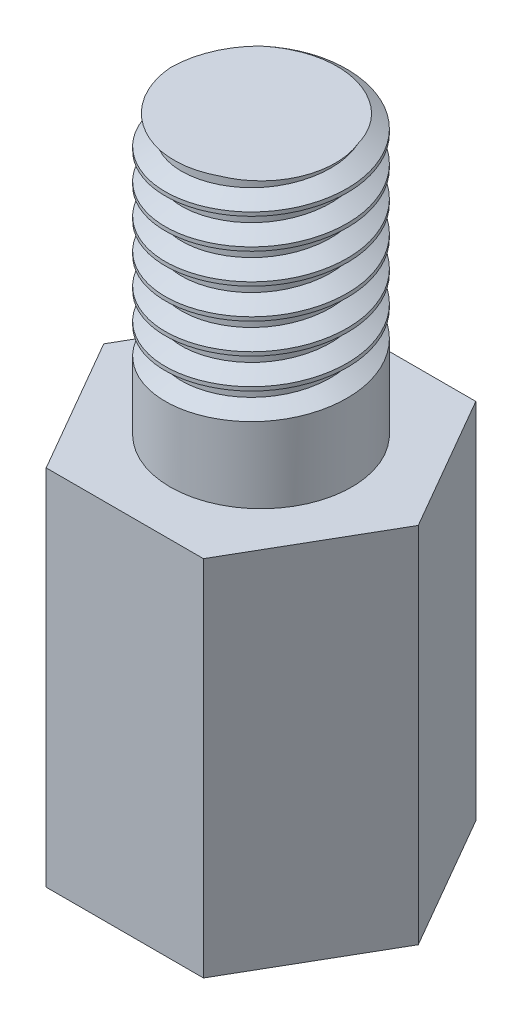
SolidWorks part; units mm, degrees
ref_plane "Front Plane" through (0, 0, 0) normal (0, 0, 1) x (1, 0, 0)
ref_plane "Top Plane" through (0, 0, 0) normal (0, 1, 0) x (1, 0, 0)
ref_plane "Right Plane" through (0, 0, 0) normal (1, 0, 0) x (0, 0, -1)
sketch "Sketch1" plane through (0, 0, 0) normal (0, 1, 0) x (1, 0, 0)
  line L1 (-2.5981, 0) -> (-1.299, -2.25)
  line L2 (-1.299, -2.25) -> (1.299, -2.25)
  line L3 (1.299, -2.25) -> (2.5981, 0)
  line L4 (2.5981, 0) -> (1.299, 2.25)
  line L5 (1.299, 2.25) -> (-1.299, 2.25)
  line L6 (-1.299, 2.25) -> (-2.5981, 0)
  circle A0 centre (0, 0) radius 2.25 construction
  dimension "D1" = 4.5
extrude "Boss-Extrude1" add sketch "Sketch1" along normal blind 6
sketch "Sketch2" plane through (0, 6, 0) normal (0, 1, 0) x (1, 0, 0)
  circle A0 centre (0, 0) radius 1.5
  dimension "D1" = 3
extrude "Boss-Extrude2" add sketch "Sketch2" along normal blind 4.5
thread "Thread1" pitch 0.5 method cut trim with start face yes profile "Thread Profile1" start angle 0, offset 1, length 4, pitch 0.5, diameter 3
ref_plane "Plane1" through (-1.5, 11.5, 0) normal (0, 0, 1) x (-1, 0, 0)
sketch "Thread Profile1" plane through (-1.5, 11.5, 0) normal (0, 0, 1) x (-1, 0, 0)
  line L0 (0, 0) -> (0, 0.5) construction
  line L11 (0, 0) -> (0, 0.4375)
  line L12 (0, 0.4375) -> (-0.2706, 0.2812)
  line L13 (-0.2706, 0.2812) -> (-0.2706, 0.1562)
  line L15 (-0.2706, 0.1562) -> (0, 0)
  line L17 (-0.2706, 0.2187) -> (0, 0.2187) construction
  point P2 (0, 0)
  dimension "Pitch" = 0.5
  dimension "Profile_Angle" = 60
  dimension "Profile_Land" = 0.125
  dimension "Profile_Height" = 0.2706
sketch "Sketch7" plane through (0, 0, 0) normal (0, -1, 0) x (1, 0, 0)
  circle A0 centre (0, 0) radius 1.5
  dimension "D1" = 3
extrude "Cut-Extrude1" cut sketch "Sketch7" against normal blind 5
thread "Thread2" pitch 0.5 method extrude profile "Thread Profile2" start angle 0, offset 0, length 5, pitch 0.5, diameter 3
ref_plane "Plane2" through (1.5, 0, 0) normal (0, 0, 1) x (1, 0, 0)
sketch "Thread Profile2" plane through (1.5, 0, 0) normal (0, 0, 1) x (1, 0, 0)
  line L0 (0, 0) -> (0, 0.5) construction
  line L11 (0, 0) -> (0, 0.4375)
  line L12 (0, 0.4375) -> (-0.2706, 0.2812)
  line L13 (-0.2706, 0.2812) -> (-0.2706, 0.1562)
  line L15 (-0.2706, 0.1562) -> (0, 0)
  line L17 (-0.2706, 0.2187) -> (0, 0.2187) construction
  point P2 (0, 0)
  dimension "Pitch" = 0.5
  dimension "Profile_Angle" = 60
  dimension "Profile_Land" = 0.125
  dimension "Profile_Height" = 0.2706
